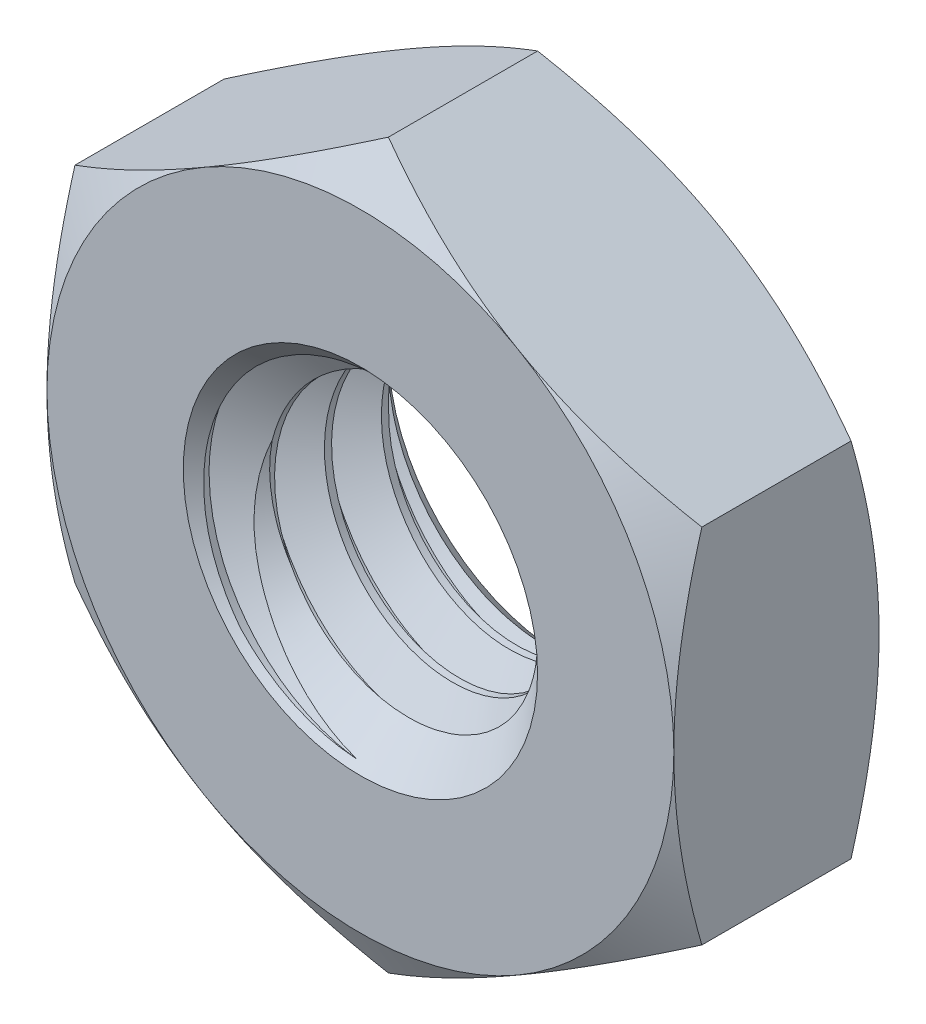
SolidWorks part; units mm, degrees
other "Markup1"
sketch "Sketch11" plane through (-2.75, 3.1754, 0.9366) normal (-0.0368, 0.4225, 0.9056) x (0.9992, 0, 0.0406)
ref_plane "Front Plane" through (0, 0, 0) normal (0, 0, 1) x (1, 0, 0)
ref_plane "Top Plane" through (0, 0, 0) normal (0, 1, 0) x (1, 0, 0)
ref_plane "Right Plane" through (0, 0, 0) normal (1, 0, 0) x (0, 0, -1)
sketch "Sketch1" plane through (0, 0, 0) normal (0, 0, 1) x (1, 0, 0)
  line L1 (0, 3.1754) -> (-2.75, 1.5877)
  line L2 (-2.75, 1.5877) -> (-2.75, -1.5877)
  line L3 (-2.75, -1.5877) -> (0, -3.1754)
  line L4 (0, -3.1754) -> (2.75, -1.5877)
  line L5 (2.75, -1.5877) -> (2.75, 1.5877)
  line L6 (2.75, 1.5877) -> (0, 3.1754)
  circle A0 centre (0, 0) radius 2.75 construction
  dimension "Width" = 5.5
sketch "Sketch2" plane through (0, 0, 0) normal (1, 0, 0) x (0, 0, -1)
  line L0 (-0.9, 0) -> (0.9, 0) construction
  line L1 (-0.9, 0) -> (-0.9, 1.5)
  line L2 (-0.9, 1.5) -> (0.9, 1.5)
  line L3 (0.9, 1.5) -> (0.9, 0)
  line L4 (0.8688, 1.5541) -> (1.1188, 1.1211) construction
  line L5 (1.1188, 1.1211) -> (1.3688, 1.5541) construction
  line L6 (1.3688, 1.5541) -> (0.8688, 1.5541) construction
  line L7 (0.8844, 1.5271) -> (1.3531, 1.5271)
  line L8 (1.3531, 1.5271) -> (1.15, 1.1752)
  line L9 (1.15, 1.1752) -> (1.0875, 1.1752)
  line L10 (1.0875, 1.1752) -> (0.8844, 1.5271)
  line L11 (1.1188, 1.1752) -> (1.1188, 1.1211) construction
  line L12 (0.9, 1.5) -> (1.3375, 1.5) construction
  line L13 (1.1188, 1.5541) -> (1.1188, 1.5) construction
  line L14 (-0.9, -1.5) -> (0.9, -1.5)
  line L15 (0, 2.75) -> (0, -2.75) construction
  line L16 (0, 2.75) -> (0, -2.75) construction
  point P2 (0, 0)
  point P18 (1.1188, 1.5271)
  point P19 (-0.9, 2.75)
  point P21 (0.9, 2.75)
  point P22 (-0.9, -1.5)
  dimension "Height" = 1.8
  dimension "Thread Size" = 3
  dimension "Thread Pitch" = 0.5
  dimension "D2" = 0.0625
sketch "Sketch3" plane through (0, 0, 0) normal (0, 0, 1) x (1, 0, 0)
  line L0 (2.75, 1.5877) -> (0, 3.1754) construction
  line L1 (2.75, -1.5877) -> (2.75, 1.5877) construction
  line L2 (0, -3.1754) -> (2.75, -1.5877) construction
  line L3 (-2.75, -1.5877) -> (0, -3.1754) construction
  line L4 (-2.75, 1.5877) -> (-2.75, -1.5877) construction
  line L5 (0, 3.1754) -> (-2.75, 1.5877) construction
  line L6 (2.75, 1.5877) -> (0, 3.1754)
  line L7 (2.75, -1.5877) -> (2.75, 1.5877)
  line L8 (0, -3.1754) -> (2.75, -1.5877)
  line L9 (-2.75, -1.5877) -> (0, -3.1754)
  line L10 (-2.75, 1.5877) -> (-2.75, -1.5877)
  line L11 (0, 3.1754) -> (-2.75, 1.5877)
extrude "Boss-Extrude1" add sketch "Sketch3" along normal up to vertex (0.9 mm away) from vertex up to point (0, 0, 0.9) starting at point (0, 0, -0.9)
sketch "Sketch4" plane through (0, 0, 0.9) normal (0, 0, 1) x (1, 0, 0)
  circle A0 centre (0, 0) radius 2.75 construction
  circle A1 centre (0, 0) radius 2.75
extrude "Cut-Extrude1" cut sketch "Sketch4" against normal through all draft 60 flip side to cut
sketch "Sketch5" plane through (0, 0, -0.9) normal (0, 0, -1) x (-1, 0, 0)
  circle A0 centre (0, 0) radius 2.75 construction
  circle A1 centre (0, 0) radius 2.75
extrude "Cut-Extrude2" cut sketch "Sketch5" against normal through all draft 60 flip side to cut
sketch "Sketch6" plane through (0, 0, 0) normal (1, 0, 0) x (0, 0, -1)
  line L1 (-0.9, 0) -> (0.9, 0)
  line L2 (-0.9, 0) -> (-0.9, 1.5)
  line L3 (-0.9, 1.5) -> (0.9, 1.5)
  line L4 (0.9, 0) -> (0.9, 1.5)
revolve "Cut-Revolve1" cut sketch "Sketch6" angle 360 about L1
sketch "Sketch7" plane through (0, 0, -0.9) normal (0, 0, -1) x (-1, 0, 0)
  circle A0 centre (0, 0) radius 1.5 construction
  circle A1 centre (0, 0) radius 1.5
curve "Helix/Spiral1" pitch 0.5 height 2.3 radius 1.5 centre (0, 0, -0.9) axis (0, 0, 1) start towards (0, 1, 0)
sketch "Sketch8" plane through (0, 0, 0) normal (1, 0, 0) x (0, 0, -1)
  line L0 (0.8844, 1.5271) -> (1.3531, 1.5271) construction
  line L1 (1.0875, 1.1752) -> (0.8844, 1.5271) construction
  line L2 (1.15, 1.1752) -> (1.0875, 1.1752) construction
  line L3 (1.3531, 1.5271) -> (1.15, 1.1752) construction
  line L4 (0.8844, 1.5271) -> (1.3531, 1.5271)
  line L5 (1.0875, 1.1752) -> (0.8844, 1.5271)
  line L6 (1.15, 1.1752) -> (1.0875, 1.1752)
  line L7 (1.3531, 1.5271) -> (1.15, 1.1752)
sweep "Sweep1" add profiles "Sketch8" path "Helix/Spiral1"
sketch "Sketch9" plane through (0, 0, -0.9) normal (0, 0, -1) x (-1, 0, 0)
  circle A0 centre (0, 0) radius 1.5541
extrude "Cut-Extrude3" cut sketch "Sketch9" against normal through all draft 45 and the other way through all
sketch "Sketch10" plane through (0, 0, 0.9) normal (0, 0, 1) x (1, 0, 0)
  circle A1 centre (0, 0) radius 1.5541
  circle A2 centre (0, 0) radius 1.5541
  dimension "D1" = 0
extrude "Cut-Extrude4" cut sketch "Sketch10" against normal through all draft 45 and the other way through all
equation "\"D2@Sketch2\" = \"Thread Pitch@Sketch2\" / 8"
equation "\"D4@Helix/Spiral1\"=\"Thread Pitch@Sketch2\""
equation "\"D3@Helix/Spiral1\" = \"Height@Sketch2\" + \"Thread Pitch@Sketch2\""
